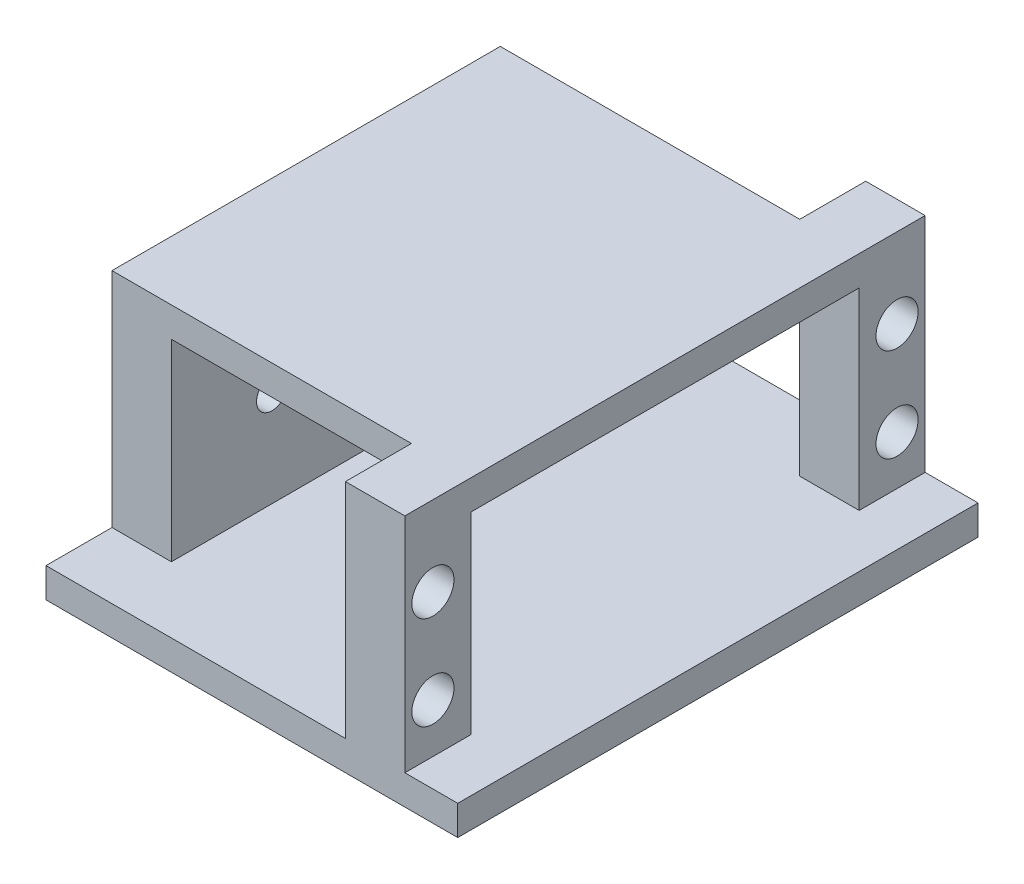
SolidWorks part; units mm, degrees
ref_plane "Front Plane" through (0, 0, 0) normal (0, 0, 1) x (1, 0, 0)
ref_plane "Top Plane" through (0, 0, 0) normal (0, 1, 0) x (1, 0, 0)
ref_plane "Right Plane" through (0, 0, 0) normal (1, 0, 0) x (0, 0, -1)
sketch "Sketch1" plane through (0, 0, 0) normal (0, 1, 0) x (1, 0, 0)
  line L1 (-22, 27.8) -> (22, 27.8)
  line L2 (-22, 27.8) -> (-22, -27.8)
  line L3 (-22, -27.8) -> (22, -27.8)
  line L4 (22, 27.8) -> (22, -27.8)
  line L5 (-22, 27.8) -> (22, -27.8) construction
  line L6 (-22, -27.8) -> (22, 27.8) construction
  point P0 (0, 0)
  dimension "D1" = 55.6
  dimension "D2" = 44
extrude "Boss-Extrude1" add sketch "Sketch1" along normal blind 3.175
sketch "Sketch2" plane through (0, 3.175, 0) normal (0, 1, 0) x (1, 0, 0)
  line L0 (-22, 27.8) -> (-22, -27.8) construction
  line L1 (-15.65, 20.75) -> (-22, 20.75)
  line L2 (-15.65, 20.75) -> (-15.65, -20.75)
  line L3 (-15.65, -20.75) -> (-22, -20.75)
  line L4 (-22, 20.75) -> (-22, -20.75)
  line L5 (-15.65, 20.75) -> (-22, -20.75) construction
  line L6 (-15.65, -20.75) -> (-22, 20.75) construction
  line L8 (-22, -27.8) -> (22, -27.8) construction
  line L9 (-22, 0) -> (65.8452, 0) construction
  line L12 (10, 27.8) -> (10, 20.75)
  line L13 (16.35, -27.8) -> (10, -27.8)
  line L14 (16.35, -27.8) -> (16.35, -20.75)
  line L15 (16.35, -20.75) -> (10, -20.75)
  line L16 (10, -27.8) -> (10, -20.75)
  line L17 (16.35, 20.75) -> (10, 20.75)
  line L18 (16.35, 27.8) -> (16.35, 20.75)
  line L19 (16.35, 27.8) -> (10, 27.8)
  line L20 (16.35, -22.55) -> (16.35, -26.8729) construction
  line L21 (-3.55, -20.1) -> (16.25, -20.1) construction
  line L22 (24.4408, 20.1) -> (19.55, 20.1) construction
  point P0 (-18.825, 0)
  dimension "D1" = 6.35
  dimension "D4" = 6.35
  dimension "D6" = 7.05
  dimension "D5" = 0
  dimension "D7" = 0.65
  dimension "D8" = 0.65
  dimension "D9" = 41.5
  dimension "D2" = 41.5
extrude "Boss-Extrude2" add sketch "Sketch2" along normal blind 20.6
sketch "Sketch3" plane through (0, 23.775, 0) normal (0, 1, 0) x (1, 0, 0)
  line L0 (-22, 20.75) -> (10, 20.75)
  line L16 (16.35, -27.8) -> (10, -27.8)
  line L17 (10, -27.8) -> (10, -20.75)
  line L18 (10, -20.75) -> (-22, -20.75)
  line L19 (-22, -20.75) -> (-22, 20.75)
  line L20 (10, 20.75) -> (10, 27.8)
  line L21 (10, 27.8) -> (16.35, 27.8)
  line L22 (16.35, 27.8) -> (16.35, -27.8)
extrude "Boss-Extrude3" add sketch "Sketch3" along normal blind 3.175
sketch "Sketch5" plane through (16.35, 0, 0) normal (1, 0, 0) x (0, 0, -1)
  line L0 (-27.8, 26.95) -> (-27.8, 3.175) construction
  line L1 (-27.8, 3.175) -> (-20.75, 3.175) construction
  line L2 (0, 0) -> (0, 26.95) construction
  line L3 (-27.8, 26.95) -> (27.8, 26.95) construction
  circle A0 centre (-24.8, 8.425) radius 2.25
  circle A1 centre (-24.8, 18.425) radius 2.25
  circle A2 centre (24.8, 18.425) radius 2.25
  circle A3 centre (24.8, 8.425) radius 2.25
  point P13 (0, 0)
  dimension "D1" = 4.5
  dimension "D3" = 5.25
  dimension "D2" = 3
  dimension "D4" = 10
extrude "Cut-Extrude2" cut sketch "Sketch5" against normal up to surface (6.35 mm away) up to face at (10, 16.805, 23.57)
sketch "Sketch6" plane through (-22, 0, 0) normal (-1, 0, 0) x (0, 0, 1)
  circle A0 centre (10, 13.43) radius 1.65
  circle A1 centre (10, 13.425) radius 1.25 construction
  point P2 (0, 0)
  dimension "D1" = 3.3
  dimension "D2" = 0
extrude "Cut-Extrude3" cut sketch "Sketch6" against normal up to surface (6.35 mm away) contours A0 up to face at (-15.65, 13.475, 0)
equation "\"D4@Sketch2\"=\"D1@Sketch2\""
equation "\"D2@Sketch2\"=\"D9@Sketch2\""
